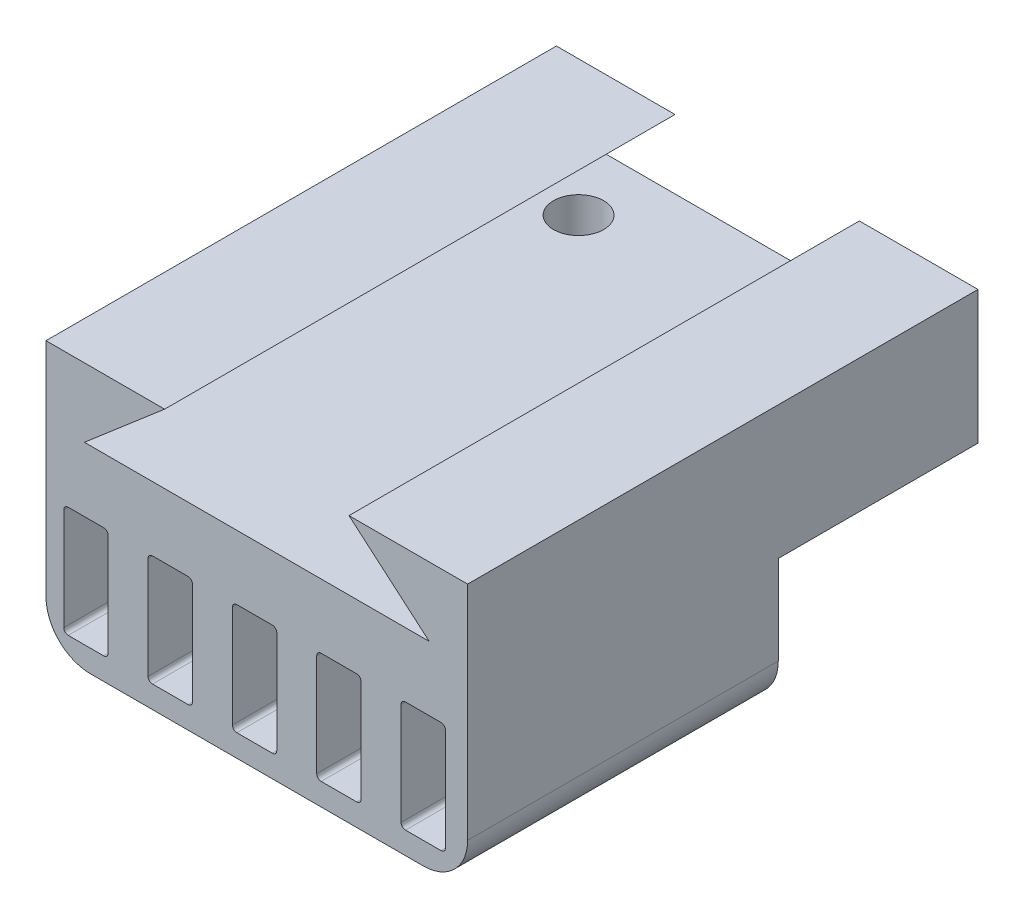
SolidWorks part; units mm, degrees
material "PLA"
ref_plane "Front" through (0, 0, 0) normal (0, 0, 1) x (1, 0, 0)
ref_plane "Top" through (0, 0, 0) normal (0, 1, 0) x (1, 0, 0)
ref_plane "Right" through (0, 0, 0) normal (1, 0, 0) x (0, 0, -1)
sketch "Sketch1" plane through (0, 0, 0) normal (0, 0, 1) x (1, 0, 0)
  line L0 (5.08, -21.59) -> (-5.08, -21.59)
  line L5 (-5.1627, -21.4936) -> (5.1627, -21.4936)
  line L6 (-5.1627, -21.4936) -> (-9.8683, -25.527)
  line L7 (-9.8683, -25.527) -> (9.8683, -25.527)
  line L8 (9.8683, -25.527) -> (5.1627, -21.4936)
  line L9 (-5.08, -21.59) -> (-5.2751, -21.59)
  line L10 (5.08, -21.59) -> (5.2751, -21.59)
  line L11 (-5.08, -21.59) -> (-5.2751, -21.59)
  line L12 (9.525, -21.59) -> (9.525, -17.6598)
  line L13 (5.08, -21.59) -> (9.525, -21.59)
  line L14 (9.525, -25.4) -> (5.08, -21.59)
  line L15 (-9.525, -25.4) -> (9.525, -25.4)
  line L16 (-5.08, -21.59) -> (-9.525, -25.4)
  line L17 (-9.525, -21.59) -> (-5.08, -21.59)
  line L18 (-9.525, -17.6598) -> (-9.525, -21.59)
  line L19 (9.525, -21.59) -> (9.525, -17.6598)
  line L20 (5.08, -21.59) -> (9.525, -21.59)
  line L21 (9.525, -25.4) -> (5.08, -21.59)
  line L22 (-9.525, -25.4) -> (9.525, -25.4)
  line L23 (-5.08, -21.59) -> (-9.525, -25.4)
  line L24 (-9.525, -21.59) -> (-5.08, -21.59)
  line L25 (-9.525, -17.6598) -> (-9.525, -21.59)
  line L27 (-12.065, -29.21) -> (12.065, -29.21)
  line L28 (-12.065, -29.21) -> (-12.065, -21.59)
  line L29 (-12.065, -21.59) -> (12.065, -21.59)
  line L30 (12.065, -29.21) -> (12.065, -21.59)
  arc A2 (-20.6375, -11.1054) -> (-19.2555, -10.6965) centre (-20.6375, -8.5654) ccw
  arc A3 (19.2555, -10.6965) -> (20.6375, -11.1054) centre (20.6375, -8.5654) ccw
  arc A4 (-20.6375, -11.1054) -> (-19.2555, -10.6965) centre (-20.6375, -8.5654) ccw
  arc A5 (19.2555, -10.6965) -> (20.6375, -11.1054) centre (20.6375, -8.5654) ccw
  ellipse E2 centre (0, 0) end of major axis (25.4, 0) minor radius 19.05 (-20.6375, -11.1054) -> (-9.525, -17.6598) ccw
  ellipse E3 centre (0, 0) end of major axis (25.4, 0) minor radius 19.05 (9.525, -17.6598) -> (20.6375, -11.1054) ccw
  ellipse E4 centre (0, 0) end of major axis (25.4, 0) minor radius 19.05 (-20.6375, -11.1054) -> (-9.525, -17.6598) ccw
  ellipse E5 centre (0, 0) end of major axis (25.4, 0) minor radius 19.05 (9.525, -17.6598) -> (20.6375, -11.1054) ccw
  spline S1 degree 3 poles (-2166.445, -15849.0793) (-418.6607, -134.144) (57.4604, 23.5329) (18.4102, -11.4784) (18.1685, -11.6861) (17.4022, -12.3125) (16.8339, -12.7373) (15.8949, -13.3659) (15.5674, -13.5742) (14.8823, -13.9857) (14.5239, -14.1894) (13.7828, -14.586) (13.3995, -14.7793) (12.6066, -15.1542) (12.1964, -15.336) (11.3542, -15.6842) (10.9219, -15.8506) (10.0343, -16.1671) (9.5775, -16.3175) (8.1859, -16.7374) (7.2281, -16.9768) (5.7448, -17.2706) (5.2427, -17.3576) (4.2222, -17.5087) (3.7022, -17.5728) (2.6581, -17.6756) (2.1332, -17.7144) (1.0777, -17.7665) (0.5456, -17.7797) (-1.0381, -17.7806) (-2.0822, -17.7301) (-3.6313, -17.5808) (-4.1449, -17.5187) (-5.1662, -17.3701) (-5.6756, -17.2832) (-6.6756, -17.0872) (-7.1675, -16.9781) (-8.1355, -16.7387) (-8.6125, -16.608) (-9.5437, -16.3283) (-9.9984, -16.1792) (-10.887, -15.8637) (-11.3215, -15.697) (-12.5878, -15.1754) (-13.3817, -14.7994) (-14.8691, -14.0059) (-15.5563, -13.5917) (-16.8227, -12.7456) (-17.3958, -12.3175) (-61.9722, 24.1081) (359.4859, -21.3348) (4215.4566, -15431.1683) knots -5.38 -5.38 -5.38 -5.38 0.03125 0.03125 0.0625 0.0625 0.125 0.125 0.15625 0.15625 0.1875 0.1875 0.21875 0.21875 0.25 0.25 0.28125 0.28125 0.3125 0.3125 0.375 0.375 0.40625 0.40625 0.4375 0.4375 0.46875 0.46875 0.5 0.5 0.5625 0.5625 0.59375 0.59375 0.625 0.625 0.65625 0.65625 0.6875 0.6875 0.71875 0.71875 0.75 0.75 0.8125 0.8125 0.875 0.875 0.9375 0.9375 6.300617 6.300617 6.300617 6.300617 only from (19.2555, -10.6965) to (-19.2555, -10.6965)
  spline S2 degree 3 poles (19.2555, -10.6965) (19.0657, -10.8817) (18.8587, -11.0763) (18.4102, -11.4784) (18.1685, -11.6861) (17.4022, -12.3125) (16.8339, -12.7373) (15.8949, -13.3659) (15.5674, -13.5742) (14.8823, -13.9857) (14.5239, -14.1894) (13.7828, -14.586) (13.3995, -14.7793) (12.6066, -15.1542) (12.1964, -15.336) (11.3542, -15.6842) (10.9219, -15.8506) (10.0343, -16.1671) (9.5775, -16.3175) (8.1859, -16.7374) (7.2281, -16.9768) (5.7448, -17.2706) (5.2427, -17.3576) (4.2222, -17.5087) (3.7022, -17.5728) (2.6581, -17.6756) (2.1332, -17.7144) (1.0777, -17.7665) (0.5456, -17.7797) (-1.0381, -17.7806) (-2.0822, -17.7301) (-3.6313, -17.5808) (-4.1449, -17.5187) (-5.1662, -17.3701) (-5.6756, -17.2832) (-6.6756, -17.0872) (-7.1675, -16.9781) (-8.1355, -16.7387) (-8.6125, -16.608) (-9.5437, -16.3283) (-9.9984, -16.1792) (-10.887, -15.8637) (-11.3215, -15.697) (-12.5878, -15.1754) (-13.3817, -14.7994) (-14.8691, -14.0059) (-15.5563, -13.5917) (-16.8227, -12.7456) (-17.3958, -12.3175) (-18.4228, -11.4783) (-18.8731, -11.0698) (-19.2555, -10.6965) knots 0 0 0 0 0.03125 0.03125 0.0625 0.0625 0.125 0.125 0.15625 0.15625 0.1875 0.1875 0.21875 0.21875 0.25 0.25 0.28125 0.28125 0.3125 0.3125 0.375 0.375 0.40625 0.40625 0.4375 0.4375 0.46875 0.46875 0.5 0.5 0.5625 0.5625 0.59375 0.59375 0.625 0.625 0.65625 0.65625 0.6875 0.6875 0.71875 0.71875 0.75 0.75 0.8125 0.8125 0.875 0.875 0.9375 0.9375 1 1 1 1
  dimension "D1" = 0
  dimension "D2" = 2.54
  dimension "D3" = 2.54
  dimension "D4" = 7.62
  dimension "D5" = 0.127
extrude "Boss-Extrude2" add sketch "Sketch1" along normal blind 25.4 contours L27 L30 L29 L20 L8 L7 L6 L24 L28 region at (0, -26.1881, 0)
sketch "Sketch3" plane through (0, -29.21, 0) normal (0, -1, 0) x (-1, 0, 0)
  line L0 (12.065, -25.4) -> (12.065, 0) construction
  line L1 (-12.065, -25.4) -> (12.065, -25.4)
  line L2 (-12.065, -25.4) -> (-12.065, -7.62)
  line L3 (-12.065, -7.62) -> (12.065, -7.62)
  line L4 (12.065, -25.4) -> (12.065, -7.62)
  dimension "D1" = 17.78
extrude "Boss-Extrude3" add sketch "Sketch3" along normal blind 7.62
sketch "Sketch4" plane through (0, 0, 25.4) normal (0, 0, 1) x (1, 0, 0)
  line L0 (12.065, -36.83) -> (-12.065, -36.83) construction
  line L1 (10.541, -35.56) -> (8.509, -35.56)
  line L2 (10.795, -35.306) -> (10.795, -29.464)
  line L3 (10.541, -29.21) -> (8.509, -29.21)
  line L4 (8.255, -35.306) -> (8.255, -29.464)
  line L5 (12.065, -36.83) -> (12.065, -21.59) construction
  line L6 (5.969, -35.306) -> (5.969, -29.464)
  line L7 (5.715, -35.56) -> (3.683, -35.56)
  line L8 (3.429, -35.306) -> (3.429, -29.464)
  line L9 (5.715, -29.21) -> (3.683, -29.21)
  line L10 (1.143, -35.306) -> (1.143, -29.464)
  line L11 (0.889, -35.56) -> (-1.143, -35.56)
  line L12 (-1.397, -35.306) -> (-1.397, -29.464)
  line L13 (0.889, -29.21) -> (-1.143, -29.21)
  line L14 (-3.683, -35.306) -> (-3.683, -29.464)
  line L15 (-3.937, -35.56) -> (-5.969, -35.56)
  line L16 (-6.223, -35.306) -> (-6.223, -29.464)
  line L17 (-3.937, -29.21) -> (-5.969, -29.21)
  line L18 (-8.509, -35.306) -> (-8.509, -29.464)
  line L19 (-8.763, -35.56) -> (-10.795, -35.56)
  line L20 (-11.049, -35.306) -> (-11.049, -29.464)
  line L21 (-8.763, -29.21) -> (-10.795, -29.21)
  arc A0 (8.509, -29.21) -> (8.255, -29.464) centre (8.509, -29.464) ccw
  arc A1 (10.795, -29.464) -> (10.541, -29.21) centre (10.541, -29.464) ccw
  arc A2 (8.509, -35.56) -> (8.255, -35.306) centre (8.509, -35.306) cw
  arc A3 (10.541, -35.56) -> (10.795, -35.306) centre (10.541, -35.306) ccw
  arc A4 (5.715, -35.56) -> (5.969, -35.306) centre (5.715, -35.306) ccw
  arc A5 (5.969, -29.464) -> (5.715, -29.21) centre (5.715, -29.464) ccw
  arc A6 (3.683, -35.56) -> (3.429, -35.306) centre (3.683, -35.306) cw
  arc A7 (3.683, -29.21) -> (3.429, -29.464) centre (3.683, -29.464) ccw
  arc A8 (0.889, -35.56) -> (1.143, -35.306) centre (0.889, -35.306) ccw
  arc A9 (1.143, -29.464) -> (0.889, -29.21) centre (0.889, -29.464) ccw
  arc A10 (-1.143, -35.56) -> (-1.397, -35.306) centre (-1.143, -35.306) cw
  arc A11 (-1.143, -29.21) -> (-1.397, -29.464) centre (-1.143, -29.464) ccw
  arc A12 (-3.937, -35.56) -> (-3.683, -35.306) centre (-3.937, -35.306) ccw
  arc A13 (-3.683, -29.464) -> (-3.937, -29.21) centre (-3.937, -29.464) ccw
  arc A14 (-5.969, -35.56) -> (-6.223, -35.306) centre (-5.969, -35.306) cw
  arc A15 (-5.969, -29.21) -> (-6.223, -29.464) centre (-5.969, -29.464) ccw
  arc A16 (-8.763, -35.56) -> (-8.509, -35.306) centre (-8.763, -35.306) ccw
  arc A17 (-8.509, -29.464) -> (-8.763, -29.21) centre (-8.763, -29.464) ccw
  arc A18 (-10.795, -35.56) -> (-11.049, -35.306) centre (-10.795, -35.306) cw
  arc A19 (-10.795, -29.21) -> (-11.049, -29.464) centre (-10.795, -29.464) ccw
  point P12 (10.795, -29.21)
  point P15 (8.255, -35.56)
  point P18 (10.795, -35.56)
  dimension "D5" = 0.254
  dimension "D1" = 2.54
  dimension "D2" = 6.35
  dimension "D3" = 1.27
  dimension "D4" = 1.27
  dimension "D6" = 5
extrude "Cut-Extrude2" cut sketch "Sketch4" against normal offset from surface (16.51 mm away) 1.27 up to face at (0, -33.02, 7.62)
sketch "Sketch5" plane through (0, 0, 8.89) normal (0, 0, 1) x (1, 0, 0)
  line L3 (10.541, -29.21) -> (8.509, -29.21) construction
  line L8 (10.795, -35.306) -> (10.795, -29.464) construction
  circle A0 centre (9.525, -32.385) radius 1.143
  circle A1 centre (4.699, -32.385) radius 1.143
  circle A2 centre (-0.127, -32.385) radius 1.143
  circle A3 centre (-4.953, -32.385) radius 1.143
  circle A4 centre (-9.779, -32.385) radius 1.143
  dimension "D1" = 2.286
  dimension "D2" = 3.175
  dimension "D3" = 1.27
  dimension "D4" = 5
extrude "Cut-Extrude3" cut sketch "Sketch5" against normal blind 1.27
fillet "Fillet1" radius 2.54 2 edges at (-12.065, -36.83, 16.51) (12.065, -36.83, 16.51)
sketch "Sketch6" plane through (0, 0, 0) normal (0, 0, -1) x (-1, 0, 0)
  line L8 (-12.065, -29.21) -> (12.065, -29.21)
  line L9 (12.065, -29.21) -> (12.065, -21.59)
  line L10 (12.065, -21.59) -> (5.2751, -21.59)
  line L11 (5.2751, -21.59) -> (9.8683, -25.527)
  line L12 (9.8683, -25.527) -> (-9.8683, -25.527)
  line L13 (-9.8683, -25.527) -> (-5.2751, -21.59)
  line L14 (-5.2751, -21.59) -> (-12.065, -21.59)
  line L15 (-12.065, -21.59) -> (-12.065, -29.21)
  line L16 (-12.065, -29.21) -> (12.065, -29.21)
  line L17 (12.065, -29.21) -> (12.065, -21.59)
  line L18 (12.065, -21.59) -> (5.2751, -21.59)
  line L19 (5.2751, -21.59) -> (9.8683, -25.527)
  line L20 (9.8683, -25.527) -> (-9.8683, -25.527)
  line L21 (-9.8683, -25.527) -> (-5.2751, -21.59)
  line L22 (-5.2751, -21.59) -> (-12.065, -21.59)
  line L23 (-12.065, -21.59) -> (-12.065, -29.21)
  dimension "D1" = 0
extrude "Boss-Extrude4" add sketch "Sketch6" along normal blind 3.81
sketch "Sketch2" plane through (0, -29.21, 0) normal (0, -1, 0) x (-1, 0, 0)
  line L1 (-12.065, 3.81) -> (12.065, 3.81) construction
  line L2 (-12.065, -7.62) -> (-12.065, 3.81) construction
  line L3 (12.065, -7.62) -> (12.065, 3.81) construction
  circle A0 centre (-6.985, 0) radius 1.4351
  circle A1 centre (6.985, 0) radius 1.4351
  dimension "D1" = 2.8702
  dimension "D3" = 5.08
  dimension "D5" = 5.08
  dimension "D2" = 3.81
  dimension "D4" = 3.81
extrude "Cut-Extrude1" cut sketch "Sketch2" against normal up to surface (3.683 mm away) up to face at (0, -25.527, 10.795)
